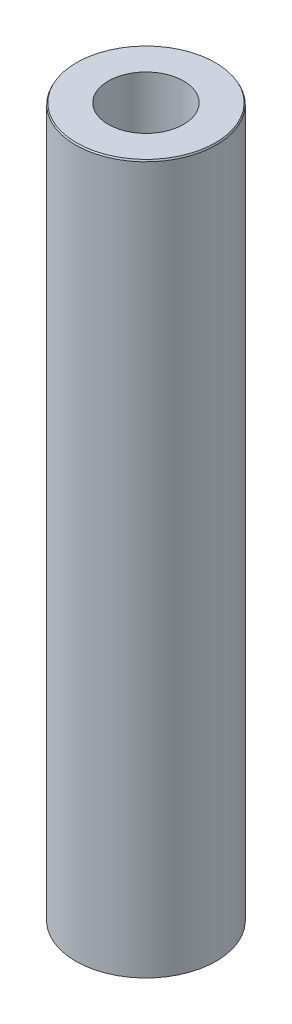
SolidWorks part; units mm, degrees
ref_plane "Front Plane" through (0, 0, 0) normal (0, 0, 1) x (1, 0, 0)
ref_plane "Top Plane" through (0, 0, 0) normal (0, 1, 0) x (1, 0, 0)
ref_plane "Right Plane" through (0, 0, 0) normal (1, 0, 0) x (0, 0, -1)
sketch "Sketch1" plane through (0, 0, 0) normal (0, 1, 0) x (1, 0, 0)
  circle A0 centre (0, 0) radius 47.5
  dimension "SHAFT_OD" = 95
extrude "Boss-Extrude1" add sketch "Sketch1" along normal blind 479.4714
sketch "Sketch2" plane through (0, 0, 0) normal (0, 1, 0) x (1, 0, 0)
  circle A0 centre (0, 0) radius 25.4496
  dimension "BORE_D" = 50.8991
extrude "Cut-Extrude1" cut sketch "Sketch2" along normal through all
chamfer "Chamfer1" distance 1.0459 angle 27.477 2 edges at (0, 479.4714, 47.5) (0, 0, 47.5) first distance on face at (0, 479.4714, 47.5) first distance on face at (0, 0, 25.4496)
